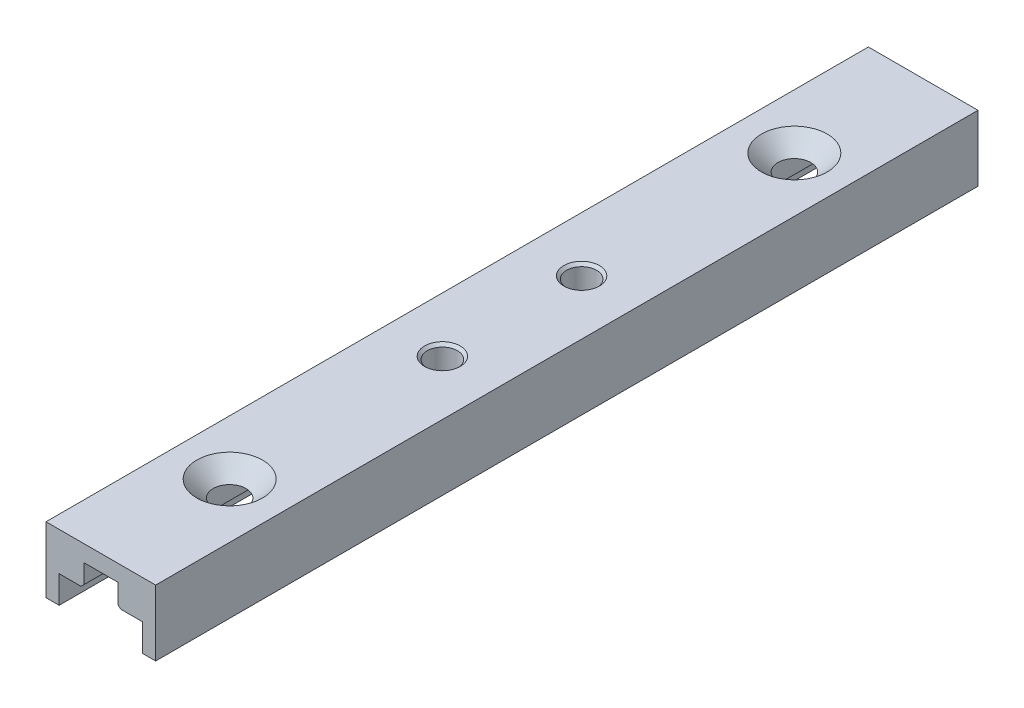
SolidWorks part; units mm, degrees
ref_plane "Front" through (0, 0, 0) normal (0, 0, 1) x (1, 0, 0)
ref_plane "Top" through (0, 0, 0) normal (0, 1, 0) x (1, 0, 0)
ref_plane "Right" through (0, 0, 0) normal (1, 0, 0) x (0, 0, -1)
sketch "Sketch1" plane through (0, 0, 0) normal (0, 0, 1) x (1, 0, 0)
  line L0 (0, 0) -> (7.6, 0)
  line L1 (7.6, 0) -> (7.6, -5)
  line L2 (7.6, -5) -> (10, -5)
  line L3 (10, -5) -> (10, 7)
  line L4 (10, 7) -> (-10, 7)
  line L5 (-10, 7) -> (-10, -5)
  line L6 (-10, -5) -> (-7.6, -5)
  line L7 (-7.6, -5) -> (-7.6, 0)
  line L8 (-7.6, 0) -> (0, 0)
  line L9 (-7.6, 0) -> (-7.6, 7) construction
  dimension "D1" = 15.2
  dimension "D2" = 2.4
  dimension "D3" = 5
  dimension "D4" = 7
extrude "Boss-Extrude1" add sketch "Sketch1" along normal blind 75 and the other way blind 75
sketch "Sketch2" plane through (0, 7, 0) normal (0, 1, 0) x (1, 0, 0)
  line L0 (0, 51.5) -> (0, 75) construction
  line L1 (10, -75) -> (-10, -75) construction
  line L2 (0, -51.5) -> (0, -75) construction
  line L4 (10, 75) -> (-10, 75) construction
  line L5 (0, -51.5) -> (0, -12.7) construction
  line L6 (0, 12.7) -> (0, 51.5) construction
  circle A0 centre (0, -51.5) radius 2.5
  circle A1 centre (0, 12.7) radius 2.75
  circle A2 centre (0, -12.7) radius 2.75
  circle A3 centre (0, 51.5) radius 2.5
  point P18 (0, 75)
  dimension "D1" = 5
  dimension "D5" = 5.5
  dimension "D2" = 23.5
  dimension "D4" = 25.4
extrude "Cut-Extrude1" cut sketch "Sketch2" against normal up to next
chamfer "Chamfer1" distance 3.5 angle 45 2 edges at (-2.5, 7, 51.5) (-2.5, 7, -51.5)
sketch "Sketch3" plane through (0, 0, 75) normal (0, 0, 1) x (1, 0, 0)
  line L0 (-7.6, 0) -> (7.6, 0) construction
  line L1 (-3.1, 0) -> (3.1, 0)
  line L2 (-3.1, 0) -> (-3.1, 4)
  line L3 (-3.1, 4) -> (3.1, 4)
  line L4 (3.1, 0) -> (3.1, 4)
  point P6 (0, 0)
  point P7 (0, 0)
  dimension "D1" = 4
  dimension "D2" = 6.2
extrude "Cut-Extrude2" cut sketch "Sketch3" against normal blind 35
mirror "Mirror2" about plane through (0, 0, 0) normal (0, 0, 1) of "Cut-Extrude2"
chamfer "Chamfer3" distance 0.5 angle 45 4 edges at (-2.75, 7, -12.7) (-2.75, 7, 12.7) (0, 0, -15.45) (0, 0, 9.95)
fillet "Fillet1" radius 1 4 edges at (-3.1, 2, -40) (3.1, 2, -40) (-3.1, 2, 40) (3.1, 2, 40)
chamfer "Chamfer2" distance 0.5 angle 45 10 edges at (-3.1, 0, 58) (0, 0, 40) (3.1, 0, 58) (-3.1, 0, -58) (0, 0, -40) (3.1, 0, -58) (-2.8071, 0, -40.2929) (2.8071, 0, -40.2929) (-2.8071, 0, 40.2929) (2.8071, 0, 40.2929)
